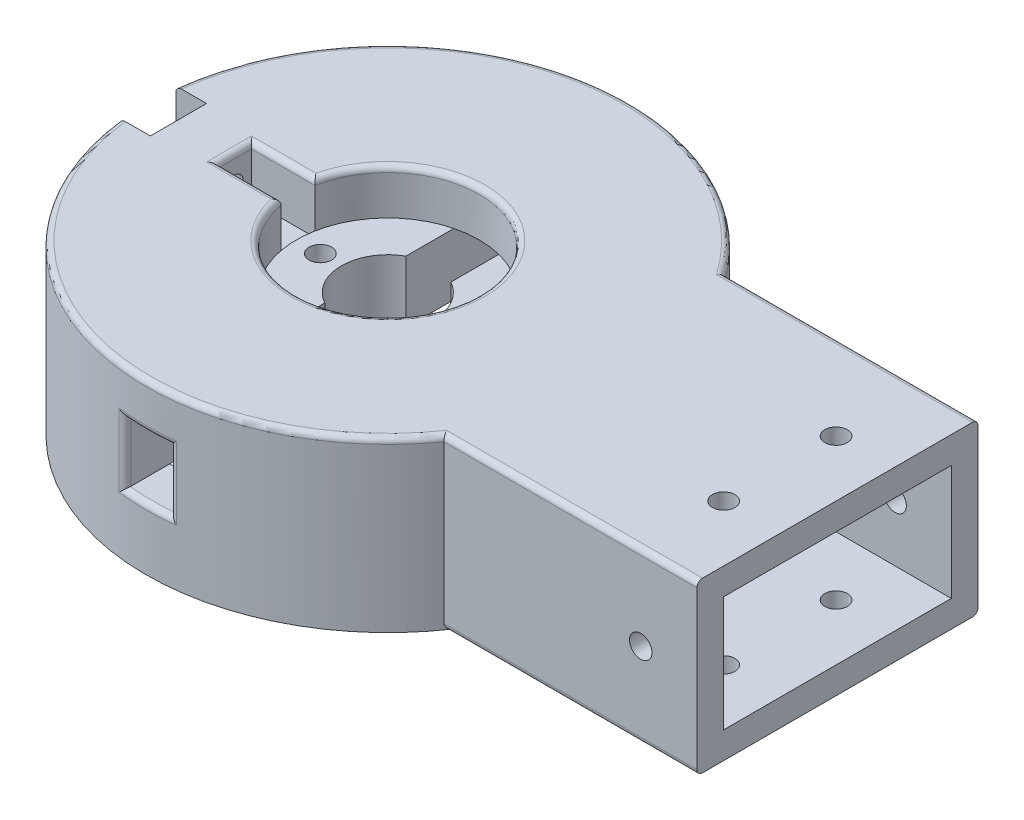
SolidWorks part; units mm, degrees
ref_plane "Front" through (0, 0, 0) normal (0, 0, 1) x (1, 0, 0)
ref_plane "Top" through (0, 0, 0) normal (0, 1, 0) x (1, 0, 0)
ref_plane "Right" through (0, 0, 0) normal (1, 0, 0) x (0, 0, -1)
sketch "Sketch1" plane through (0, 0, 0) normal (0, 0, 1) x (1, 0, 0)
  line L0 (0, 2.25) -> (0, 5)
  line L1 (0, -2.25) -> (0, -5)
  line L2 (0, -5) -> (8, -5)
  line L3 (8, -5) -> (8, 5)
  line L4 (8, 5) -> (0, 5)
  line L6 (-35, 11.0097) -> (-35, -14.1724) construction
  arc A0 (0, -2.25) -> (0, 2.25) centre (0, 0) ccw
revolve "Revolve1" add sketch "Sketch1" angle 360 about L6
sketch "Sketch2" plane through (0, 5, 0) normal (0, 1, 0) x (1, 0, 0)
  circle A0 centre (-35, 0) radius 43
extrude "Boss-Extrude1" add sketch "Sketch2" along normal blind 20
sketch "Sketch3" plane through (0, 25, 0) normal (0, 1, 0) x (1, 0, 0)
  line L1 (-0.0143, 25) -> (45, 25)
  line L3 (-0.0143, -25) -> (45, -25)
  line L4 (45, 25) -> (45, -25)
  arc A0 (-0.0143, -25) -> (-0.0143, 25) centre (-35, 0) ccw
  point P0 (-35, 0)
extrude "Boss-Extrude2" add sketch "Sketch3" against normal blind 30
sketch "Sketch4" plane through (45, 0, 0) normal (1, 0, 0) x (0, 0, -1)
  line L0 (0, 25) -> (0, -5) construction
  line L1 (-25, 25) -> (25, 25) construction
  line L2 (-25, -5) -> (25, -5) construction
  line L4 (-20.25, 20.25) -> (20.25, 20.25)
  line L5 (-20.25, 20.25) -> (-20.25, -0.25)
  line L6 (-20.25, -0.25) -> (20.25, -0.25)
  line L7 (20.25, 20.25) -> (20.25, -0.25)
  line L8 (-20.25, 20.25) -> (20.25, -0.25) construction
  line L9 (-20.25, -0.25) -> (20.25, 20.25) construction
  point P6 (0, 10)
extrude "Cut-Extrude1" cut sketch "Sketch4" against normal blind 40
sketch "Sketch5" plane through (0, 5, 0) normal (0, -1, 0) x (1, 0, 0)
  circle A0 centre (-35, 0) radius 8.25
sketch "Sketch10" plane through (0, 0, 0) normal (1, 0, 0) x (0, 0, -1)
  circle A0 centre (0, 0) radius 2.25
extrude "Cut-Extrude7" cut sketch "Sketch10" against normal blind 400
ref_plane "Plane1" through (-72.25, 0, 0) normal (1, 0, 0) x (0, 0, -1)
sketch "Sketch11" plane through (-72.25, 0, 0) normal (1, 0, 0) x (0, 0, -1)
  line L1 (-5, -37.4042) -> (5, -37.4042)
  line L2 (-5, -37.4042) -> (-5, 37.4042)
  line L3 (-5, 37.4042) -> (5, 37.4042)
  line L4 (5, -37.4042) -> (5, 37.4042)
  line L5 (-5, -37.4042) -> (5, 37.4042) construction
  line L6 (-5, 37.4042) -> (5, -37.4042) construction
  point P0 (0, 0)
extrude "Cut-Extrude8" cut sketch "Sketch11" against normal blind 400
sketch "Sketch12" plane through (0, 25, 0) normal (0, 1, 0) x (1, 0, 0)
  line L0 (-72.25, 0) -> (-62.25, 0) construction
  line L1 (-72.25, -50) -> (-72.25, 50) construction
  line L2 (-62.25, 0) -> (-42.2044, 0) construction
  line L4 (-62.25, 3) -> (-42.2044, 3)
  line L5 (-62.25, 3) -> (-62.25, -3)
  line L6 (-62.25, -3) -> (-42.2044, -3)
  line L7 (-42.2044, 3) -> (-42.2044, -3)
  line L8 (-62.25, 3) -> (-42.2044, -3) construction
  line L9 (-62.25, -3) -> (-42.2044, 3) construction
  point P5 (-52.2272, 0)
extrude "Cut-Extrude9" cut sketch "Sketch12" against normal blind 10
sketch "Sketch13" plane through (-72.25, 0, 0) normal (-1, 0, 0) x (0, 0, 1)
  circle A0 centre (0, 20) radius 1.5
extrude "Cut-Extrude10" cut sketch "Sketch13" against normal blind 10
sketch "Sketch14" plane through (0, -0.25, 0) normal (0, 1, 0) x (1, 0, 0)
  line L0 (45, -20.25) -> (45, -10.25) construction
  line L1 (45, -20.25) -> (45, 20.25) construction
  line L2 (45, -10.25) -> (35, -10.25) construction
  line L3 (35, -10.25) -> (35, 9.75) construction
  circle A0 centre (35, -10.25) radius 2
  circle A1 centre (35, 9.75) radius 2
extrude "Cut-Extrude11" cut sketch "Sketch14" against normal blind 10 and the other way blind 50
sketch "Sketch15" plane through (0, 0, 20.25) normal (0, 0, -1) x (-1, 0, 0)
  line L0 (-45, 10) -> (-35, 10) construction
  line L1 (-45, 20.25) -> (-45, -0.25) construction
  circle A0 centre (-35, 10) radius 2
extrude "Cut-Extrude12" cut sketch "Sketch15" against normal blind 10 and the other way blind 50
extrude "Cut-Extrude13" cut sketch "Sketch5" against normal blind 11
sketch "Sketch16" plane through (0, 25, 0) normal (0, 1, 0) x (1, 0, 0)
  circle A0 centre (-35, 0) radius 16.25
extrude "Cut-Extrude14" cut sketch "Sketch16" against normal blind 9
sketch "Sketch19" plane through (0, 15, 0) normal (0, 1, 0) x (1, 0, 0)
  line L0 (-62.25, 3) -> (-40.3202, 3)
  line L1 (-40.3202, 3) -> (-40.3202, -3)
  line L2 (-40.3202, -3) -> (-62.25, -3)
  line L3 (-62.25, -3) -> (-62.25, 3)
  line L4 (-62.25, 3) -> (-62.1024, 2.8746)
  arc M1 (-42.6852, -3) -> (-42.6852, 3) centre (-35, 0) cw
  line M2 (-42.6852, 3) -> (-62.25, 3)
  line M3 (-62.25, 3) -> (-62.25, -3)
  line M4 (-62.25, -3) -> (-42.6852, -3)
extrude "Boss-Extrude3" add sketch "Sketch19" along normal blind 1 contours M4 M1 M2 M3 region at (-52.6565, 15, 0)
sketch "Sketch20" plane through (0, 16, 0) normal (0, 1, 0) x (1, 0, 0)
  circle A1 centre (-23, 0) radius 2
  circle A2 centre (-47, 0) radius 2
extrude "Cut-Extrude17" cut sketch "Sketch20" against normal blind 11
sketch "Sketch21" plane through (0, 5, 0) normal (0, -1, 0) x (1, 0, 0)
  circle A0 centre (-23, 0) radius 3.5
  circle A1 centre (-47, 0) radius 3.5
extrude "Cut-Extrude18" cut sketch "Sketch21" against normal blind 4
fillet "Fillet2" radius 1 4 edges at (-56.6103, 25, 3) (-62.25, 25, 0) (-56.6103, 25, -3) (-18.75, 25, 0)
sketch "Sketch22" plane through (0, -5, 0) normal (0, -1, 0) x (1, 0, 0)
  circle A0 centre (-35, 0) radius 35
extrude "Cut-Extrude19" cut sketch "Sketch22" against normal blind 11
sketch "Sketch23" plane through (0, 16, 0) normal (0, 1, 0) x (1, 0, 0)
  circle A0 centre (-35, 0) radius 16.25
extrude "Boss-Extrude4" add sketch "Sketch23" along normal blind 1
sketch "Sketch24" plane through (0, 6, 0) normal (0, -1, 0) x (1, 0, 0)
  circle A0 centre (-47, 0) radius 2
  circle A1 centre (-23, 0) radius 2
  circle A2 centre (-35, 0) radius 8.25
extrude "Cut-Extrude20" cut sketch "Sketch24" against normal blind 100
sketch "Sketch25" plane through (0, 6, 0) normal (0, -1, 0) x (1, 0, 0)
  line L1 (-39, 52.4711) -> (-31, 52.4711)
  line L2 (-39, 52.4711) -> (-39, -52.4711)
  line L3 (-39, -52.4711) -> (-31, -52.4711)
  line L4 (-31, 52.4711) -> (-31, -52.4711)
  line L5 (-39, 52.4711) -> (-31, -52.4711) construction
  line L6 (-39, -52.4711) -> (-31, 52.4711) construction
  point P0 (-35, 0)
extrude "Cut-Extrude23" cut sketch "Sketch25" against normal blind 11
fillet "Fillet3" radius 1 14 edges at (22.4929, -5, 25) (-31, 11.5, -42.8135) (-35, 6, -43) (-35, 17, -43) (-39, 11.5, -42.8135) (-35, 17, 43) (-39, 11.5, 42.8135) (-35, 6, 43) (-31, 11.5, 42.8135) (-45.7196, 25, 41.6424) (22.4929, 25, 25) (-45.7196, 25, -41.6424) (22.4929, -5, -25) (22.4929, 25, -25)
